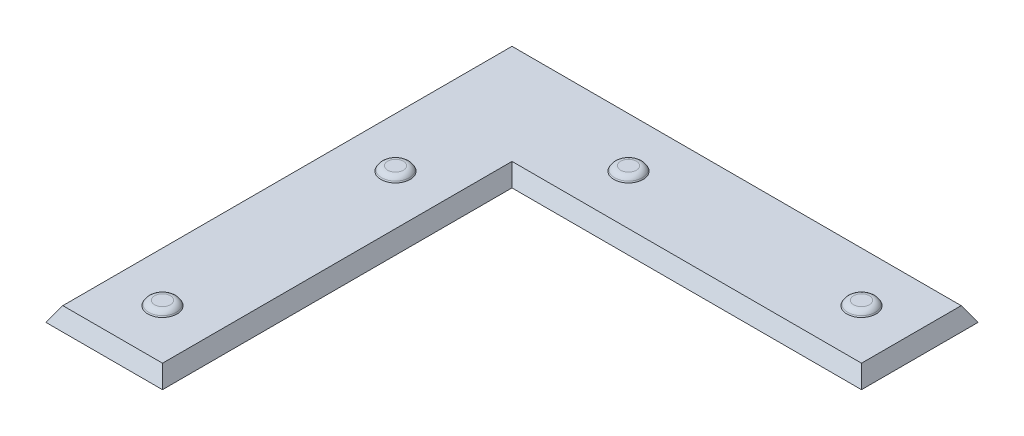
SolidWorks part; units mm, degrees
material "Brass"
ref_plane "Front Plane" through (0, 0, 0) normal (0, 0, 1) x (1, 0, 0)
ref_plane "Top Plane" through (0, 0, 0) normal (0, 1, 0) x (1, 0, 0)
ref_plane "Right Plane" through (0, 0, 0) normal (1, 0, 0) x (0, 0, -1)
ref_axis "X-Axis" through (-171.1325, 0, 0) along (1, 0, 0)
ref_axis "Y-Axis" through (0, 16.7084, 0) along (0, -1, 0)
ref_axis "Z-Axis" through (0, 0, -88.5825) along (0, 0, 1)
sketch "Sketch2" plane through (0, 15.875, 0) normal (0, 1, 0) x (1, 0, 0)
  line L0 (-169.8625, 61.9125) -> (-169.8625, 87.3125)
  line L1 (-169.8625, 87.3125) -> (-144.4625, 87.3125)
  line L2 (-144.4625, 87.3125) -> (-144.4625, 80.9625)
  line L3 (-144.4625, 80.9625) -> (-163.5125, 80.9625)
  line L4 (-163.5125, 80.9625) -> (-163.5125, 61.9125)
  line L5 (-163.5125, 61.9125) -> (-169.8625, 61.9125)
  line L6 (-163.5125, 61.9125) -> (-161.925, 61.9125) construction
  line L7 (-161.925, 34.925) -> (-161.925, 79.375) construction
  line L8 (-169.8625, 61.9125) -> (-171.45, 61.9125) construction
  line L9 (-171.45, 88.9) -> (-171.45, -88.9) construction
  line L10 (-144.4625, 80.9625) -> (-144.4625, 79.375) construction
  line L11 (-165.1, 79.375) -> (165.1, 79.375) construction
  line L12 (-144.4625, 87.3125) -> (-144.4625, 88.9) construction
  line L13 (165.1, 88.9) -> (-165.1, 88.9) construction
  dimension "D1" = 6.35
  dimension "D2" = 25.4
extrude "Boss-Extrude1" add sketch "Sketch2" along normal blind 0.7937 draft 30
sketch "Sketch3" plane through (0, 16.6687, 0) normal (0, 1, 0) x (1, 0, 0)
  line L0 (-166.6875, 62.3708) -> (-166.6875, 84.1375) construction
  line L1 (-169.4042, 62.3708) -> (-163.9708, 62.3708) construction
  line L2 (-166.6875, 84.1375) -> (-144.9208, 84.1375) construction
  line L3 (-144.9208, 81.4208) -> (-144.9208, 86.8542) construction
  line L4 (-169.8625, 61.9125) -> (-163.5125, 61.9125) construction
  line L5 (-144.4625, 80.9625) -> (-144.4625, 87.3125) construction
  circle A0 centre (-166.6875, 65.0875) radius 0.7938
  circle A1 centre (-166.6875, 77.7875) radius 0.7938
  circle A2 centre (-160.3375, 84.1375) radius 0.7938
  circle A3 centre (-147.6375, 84.1375) radius 0.7938
  dimension "D5" = 1.5875
  dimension "D1" = 3.175
  dimension "D2" = 12.7
  dimension "D3" = 3.175
  dimension "D4" = 12.7
extrude "Boss-Extrude2" add sketch "Sketch3" along normal blind 0.254 draft 30
fillet "Fillet1" radius 0.381 4 edges at (-147.6375, 16.9228, -83.4904) (-160.3375, 16.9228, -83.4904) (-166.6875, 16.9228, -77.1404) (-166.6875, 16.9228, -64.4404)
